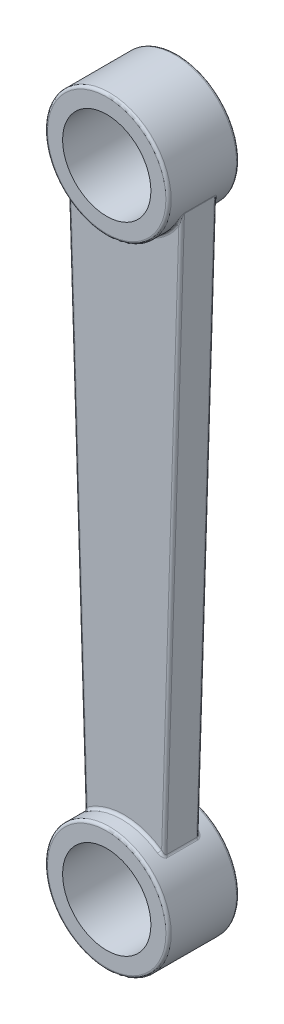
SolidWorks part; units mm, degrees
ref_plane "Front" through (0, 0, 0) normal (0, 0, 1) x (1, 0, 0)
ref_plane "Top" through (0, 0, 0) normal (0, 1, 0) x (1, 0, 0)
ref_plane "Right" through (0, 0, 0) normal (1, 0, 0) x (0, 0, -1)
sketch "Sketch1" plane through (0, 0, 0) normal (0, 0, 1) x (1, 0, 0)
  line L0 (0, 0) -> (0, -18) construction
  line L1 (-1.625, -0.6495) -> (-1.125, -16.6595)
  line L2 (1.625, -0.6495) -> (1.125, -16.6595)
  circle A0 centre (0, 0) radius 1.25
  arc A1 (1.625, -0.6495) -> (-1.625, -0.6495) centre (0, 0) ccw
  circle A2 centre (0, -18) radius 1.25
  arc A3 (-1.125, -16.6595) -> (1.125, -16.6595) centre (0, -18) ccw
  dimension "D1" = 2.25
  dimension "D2" = 3.5
  dimension "D3" = 3.25
  dimension "D4" = 3.5
  dimension "D5" = 18
extrude "Boss-Extrude1" add sketch "Sketch1" along normal blind 1
sketch "Sketch2" plane through (0, 0, 1) normal (0, 0, 1) x (1, 0, 0)
  circle A0 centre (0, 0) radius 1.25 construction
  circle A1 centre (0, 0) radius 1.25
  arc A2 (1.625, -0.6495) -> (-1.625, -0.6495) centre (0, 0) ccw construction
  circle A3 centre (0, 0) radius 1.75
extrude "Boss-Extrude2" add sketch "Sketch2" along normal blind 0.5
sketch "Sketch3" plane through (0, 0, 0) normal (0, 0, -1) x (-1, 0, 0)
  circle A0 centre (0, 0) radius 1.25 construction
  circle A1 centre (0, 0) radius 1.25
  arc A2 (1.625, -0.6495) -> (-1.625, -0.6495) centre (0, 0) ccw construction
  circle A3 centre (0, 0) radius 1.75
extrude "Boss-Extrude3" add sketch "Sketch3" along normal blind 0.5
sketch "Sketch4" plane through (0, 0, 0) normal (0, 0, -1) x (-1, 0, 0)
  arc A0 (-1.125, -16.6595) -> (1.125, -16.6595) centre (0, -18) ccw construction
  circle A1 centre (0, -18) radius 1.75
  circle A2 centre (0, -18) radius 1.25 construction
  circle A3 centre (0, -18) radius 1.25
extrude "Boss-Extrude4" add sketch "Sketch4" along normal blind 0.5
sketch "Sketch5" plane through (0, 0, 1) normal (0, 0, 1) x (1, 0, 0)
  circle A0 centre (0, -18) radius 1.25 construction
  circle A1 centre (0, -18) radius 1.25
  arc A2 (-1.125, -16.6595) -> (1.125, -16.6595) centre (0, -18) ccw construction
  circle A3 centre (0, -18) radius 1.75
extrude "Boss-Extrude5" add sketch "Sketch5" along normal blind 0.5
fillet "Fillet1" radius 0.075 16 edges at (0, -1.75, 1) (0, -1.75, 0) (0, -16.25, 0) (0, -16.25, 1) (-1.125, -16.6595, 0.5) (-1.625, -0.6495, 0.5) (-1.375, -8.6545, 0) (-1.375, -8.6545, 1) (1.625, -0.6495, 0.5) (1.375, -8.6545, 0) (1.125, -16.6595, 0.5) (1.375, -8.6545, 1) (-1.75, -18, -0.5) (-1.75, 0, -0.5) (1.75, -18, 1.5) (1.75, 0, 1.5)
